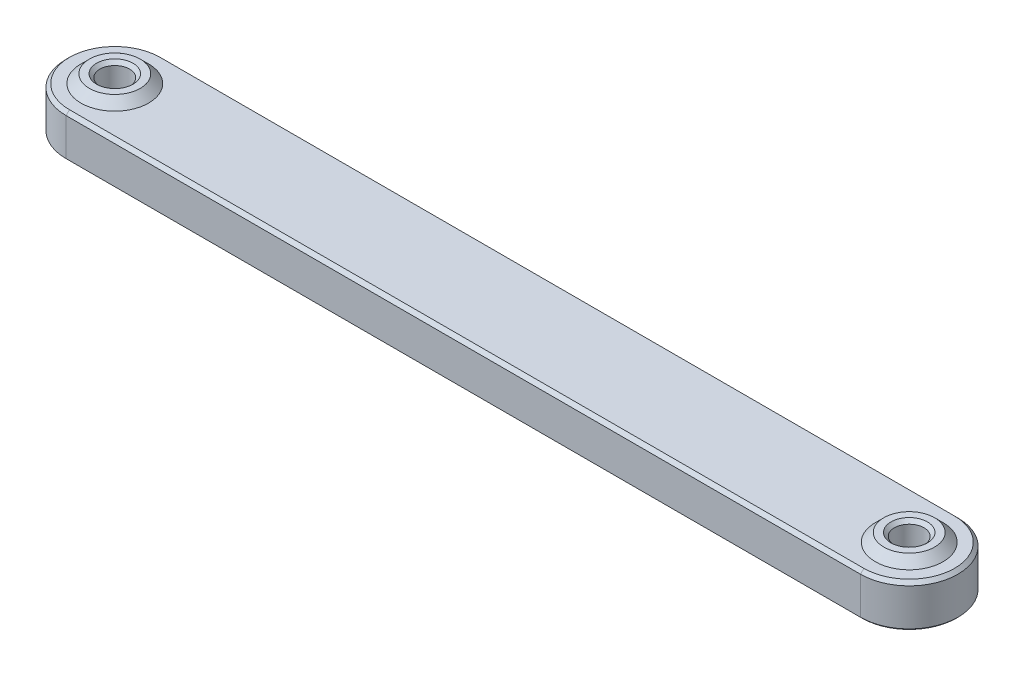
SolidWorks part; units mm, degrees
ref_plane "Alzado" through (0, 0, 0) normal (0, 0, 1) x (1, 0, 0)
ref_plane "Planta" through (0, 0, 0) normal (0, 1, 0) x (1, 0, 0)
ref_plane "Vista lateral" through (0, 0, 0) normal (1, 0, 0) x (0, 0, -1)
sketch "Croquis2" plane through (0, 0, 0) normal (0, 1, 0) x (1, 0, 0)
  line L0 (0, 0) -> (93.75, 0) construction
  line L1 (0, 5.75) -> (93.75, 5.75)
  line L2 (0, -5.75) -> (93.75, -5.75)
  arc A0 (0, 5.75) -> (0, -5.75) centre (0, 0) ccw
  arc A1 (93.75, -5.75) -> (93.75, 5.75) centre (93.75, 0) ccw
  circle A2 centre (93.75, 0) radius 1.75
  circle A3 centre (0, 0) radius 1.75
  point P3 (46.875, 0)
  dimension "D2" = 3.5
  dimension "D3" = 5.75
  dimension "D1" = 93.75
extrude "Saliente-Extruir1" add sketch "Croquis2" along normal blind 5 contours L2 A1 L1 A0 A3 A2 region at (46.875, 0, 0)
sketch "Croquis3" plane through (0, 5, 0) normal (0, 1, 0) x (1, 0, 0)
  circle A0 centre (93.75, 0) radius 3
  circle A1 centre (93.75, 0) radius 1.75 construction
  circle A2 centre (93.75, 0) radius 1.75
  circle A3 centre (0, 0) radius 3
  circle A4 centre (0, 0) radius 1.75 construction
  circle A5 centre (0, 0) radius 1.75
  dimension "D1" = 6
extrude "Saliente-Extruir2" add sketch "Croquis3" along normal blind 1
chamfer "Chaflán1" distance 1 angle 45 2 edges at (93.75, 5, 3) (0, 5, 3)
chamfer "Chaflán2" distance 0.4 angle 45 6 edges at (46.875, 5, -5.75) (-5.75, 5, 0) (99.5, 5, 0) (46.875, 5, 5.75) (93.75, 6, 1.75) (0, 6, 1.75)
sketch "Croquis4" plane through (0, 0, 0) normal (0, -1, 0) x (1, 0, 0)
  line L1 (93.75, 3.2043) -> (90.975, 1.6021)
  line L2 (90.975, 1.6021) -> (90.975, -1.6021)
  line L3 (90.975, -1.6021) -> (93.75, -3.2043)
  line L4 (93.75, -3.2043) -> (96.525, -1.6021)
  line L5 (96.525, -1.6021) -> (96.525, 1.6021)
  line L6 (96.525, 1.6021) -> (93.75, 3.2043)
  circle A0 centre (93.75, 0) radius 2.775 construction
  circle A1 centre (93.75, 3.2043) radius 0.4
  circle A2 centre (96.525, 1.6021) radius 0.4
  circle A3 centre (96.525, -1.6021) radius 0.4
  circle A4 centre (93.75, -3.2043) radius 0.4
  circle A5 centre (90.975, -1.6021) radius 0.4
  circle A6 centre (90.975, 1.6021) radius 0.4
  point P22 (93.75, 0)
  circle M9 centre (93.75, 0) radius 1.75
  dimension "D1" = 5.55
  dimension "D2" = 0.8
  dimension "D3" = 6
extrude "Cortar-Extruir1" cut sketch "Croquis4" against normal blind 2.3 contours A6 L2 A5 L3 A4 L4 A3 L5 A2 L6 A1 L1 M9 | L6 A1 L1 | L1 A1 L6 | L5 A2 L6 | L6 A2 L5 | L4 A3 L5 | L5 A3 L4 | L3 A4 L4 | L4 A4 L3 | L2 A5 L3 | L3 A5 L2 | L1 A6 L2 | L2 A6 L1 region at (93.75, 0, 2.9838) region at (93.75, 0, 3.3146) region at (93.75, 0, 2.7225) region at (91.166, 0, 1.4919) region at (90.8795, 0, 1.6573) region at (96.6205, 0, 1.6573) region at (96.334, 0, 1.4919) region at (91.166, 0, -1.4919) region at (90.8795, 0, -1.6573) region at (96.6205, 0, -1.6573) region at (96.334, 0, -1.4919) region at (93.75, 0, -2.9838) region at (93.75, 0, -3.3146)
chamfer "Chaflán3" distance 0.2 angle 45 17 edges at (99.5, 0, 0) (46.875, 0, -5.75) (-5.75, 0, 0) (46.875, 0, 5.75) (0, 0, 1.75) (90.6286, 0, -1.8021) (92.3625, 0, -2.4032) (93.75, 0, -3.6043) (95.1375, 0, -2.4032) (96.8714, 0, -1.8021) (96.525, 0, 0) (96.8714, 0, 1.8021) (95.1375, 0, 2.4032) (93.75, 0, 3.6043) (92.3625, 0, 2.4032) (90.6286, 0, 1.8021) (90.975, 0, 0)
sketch "Croquis5" plane through (0, 2.3, 0) normal (0, -1, 0) x (1, 0, 0)
  line L0 (92, 2.1939) -> (92, -2.1939)
  line L1 (93.4036, 3.0043) -> (91.3214, 1.8021) construction
  line L2 (91.3214, -1.8021) -> (93.4036, -3.0043) construction
  line L3 (93.75, 1.75) -> (93.75, -1.75) construction
  line L4 (95.5, 2.1939) -> (95.5, -2.1939)
  line L11 (90.975, 1.2021) -> (90.975, -1.2021)
  line L12 (91.3214, -1.8021) -> (93.4036, -3.0043)
  line L13 (94.0964, -3.0043) -> (96.1786, -1.8021)
  line L14 (96.525, -1.2021) -> (96.525, 1.2021)
  line L15 (96.1786, 1.8021) -> (94.0964, 3.0043)
  line L16 (93.4036, 3.0043) -> (91.3214, 1.8021)
  line L17 (90.975, 1.2021) -> (90.975, -1.2021)
  line L18 (91.3214, -1.8021) -> (93.4036, -3.0043)
  line L19 (94.0964, -3.0043) -> (96.1786, -1.8021)
  line L20 (96.525, -1.2021) -> (96.525, 1.2021)
  line L21 (96.1786, 1.8021) -> (94.0964, 3.0043)
  line L22 (93.4036, 3.0043) -> (91.3214, 1.8021)
  circle A0 centre (93.75, 0) radius 1.75 construction
  arc A7 (91.3214, 1.8021) -> (90.975, 1.2021) centre (90.975, 1.6021) ccw
  arc A8 (90.975, -1.2021) -> (91.3214, -1.8021) centre (90.975, -1.6021) ccw
  arc A9 (93.4036, -3.0043) -> (94.0964, -3.0043) centre (93.75, -3.2043) ccw
  arc A10 (96.1786, -1.8021) -> (96.525, -1.2021) centre (96.525, -1.6021) ccw
  arc A11 (96.525, 1.2021) -> (96.1786, 1.8021) centre (96.525, 1.6021) ccw
  arc A12 (94.0964, 3.0043) -> (93.4036, 3.0043) centre (93.75, 3.2043) ccw
  arc A13 (91.3214, 1.8021) -> (90.975, 1.2021) centre (90.975, 1.6021) ccw
  arc A14 (90.975, -1.2021) -> (91.3214, -1.8021) centre (90.975, -1.6021) ccw
  arc A15 (93.4036, -3.0043) -> (94.0964, -3.0043) centre (93.75, -3.2043) ccw
  arc A16 (96.1786, -1.8021) -> (96.525, -1.2021) centre (96.525, -1.6021) ccw
  arc A17 (96.525, 1.2021) -> (96.1786, 1.8021) centre (96.525, 1.6021) ccw
  arc A18 (94.0964, 3.0043) -> (93.4036, 3.0043) centre (93.75, 3.2043) ccw
  line M17 (91.3214, -1.8021) -> (93.4036, -3.0043)
  arc M18 (93.4036, -3.0043) -> (94.0964, -3.0043) centre (93.75, -3.2043) ccw
  line M19 (94.0964, -3.0043) -> (96.1786, -1.8021)
  line M23 (96.1786, 1.8021) -> (94.0964, 3.0043)
  arc M24 (94.0964, 3.0043) -> (93.4036, 3.0043) centre (93.75, 3.2043) ccw
  line M25 (93.4036, 3.0043) -> (91.3214, 1.8021)
  circle M26 centre (93.75, 0) radius 1.75
  dimension "D1" = 0
extrude "Cortar-Extruir2" cut sketch "Croquis5" against normal blind 0.2 contours L4 L0 M23 M24 M25 M26 | L4 L0 M26 M17 M18 M19 region at (93.75, 2.3, 2.0992) region at (93.75, 2.3, -2.0992)
sketch "Croquis6" plane through (0, 2.5, 0) normal (0, -1, 0) x (1, 0, 0)
  line L0 (92, 1.75) -> (95.5, 1.75)
  line L1 (92, 2.1939) -> (92, -2.1939) construction
  line L2 (95.5, 2.1939) -> (95.5, 0) construction
  line L3 (92, 0) -> (95.5, 0) construction
  line L4 (92, -1.75) -> (95.5, -1.75)
  line L5 (95.5, 0) -> (95.5, 2.1939) construction
  line L6 (95.5, 2.1939) -> (94.0964, 3.0043) construction
  line L7 (93.4036, 3.0043) -> (92, 2.1939) construction
  line L8 (92, 2.1939) -> (92, 0) construction
  line L9 (95.5, -2.1939) -> (95.5, 0) construction
  line L10 (92, 0) -> (92, -2.1939) construction
  line L11 (92, -2.1939) -> (93.4036, -3.0043) construction
  line L12 (94.0964, -3.0043) -> (95.5, -2.1939) construction
  line L13 (95.5, 0) -> (95.5, 2.1939)
  line L14 (95.5, 2.1939) -> (94.0964, 3.0043)
  line L15 (93.4036, 3.0043) -> (92, 2.1939)
  line L16 (92, 2.1939) -> (92, 0)
  line L17 (95.5, -2.1939) -> (95.5, 0)
  line L18 (92, 0) -> (92, -2.1939)
  line L19 (92, -2.1939) -> (93.4036, -3.0043)
  line L20 (94.0964, -3.0043) -> (95.5, -2.1939)
  arc A0 (95.5, 0) -> (92, 0) centre (93.75, 0) ccw construction
  arc A1 (94.0964, 3.0043) -> (93.4036, 3.0043) centre (93.75, 3.2043) ccw construction
  arc A2 (92, 0) -> (95.5, 0) centre (93.75, 0) ccw construction
  arc A3 (93.4036, -3.0043) -> (94.0964, -3.0043) centre (93.75, -3.2043) ccw construction
  arc A4 (94.0964, 3.0043) -> (93.4036, 3.0043) centre (93.75, 3.2043) ccw
  arc A5 (95.5, 0) -> (92, 0) centre (93.75, 0) ccw
  arc A6 (92, 0) -> (95.5, 0) centre (93.75, 0) ccw
  arc A7 (93.4036, -3.0043) -> (94.0964, -3.0043) centre (93.75, -3.2043) ccw
  line M3 (95.5, 0) -> (95.5, 2.1939)
  line M7 (92, 2.1939) -> (92, 0)
  arc M8 (92, 0) -> (95.5, 0) centre (93.75, 0) cw
extrude "Cortar-Extruir3" cut sketch "Croquis6" against normal blind 0.2 contours L0 M7 M8 | L0 M8 M3 | A6 L4 L17 | A6 L18 L4 region at (92.3909, 2.5, 1.3591) region at (95.1091, 2.5, 1.3591) region at (92.3909, 2.5, -1.3591) region at (95.1091, 2.5, -1.3591)
chamfer "Chaflán4" distance 0.4 angle 45 4 edges at (94.9874, 2.7, -1.2374) (92.5126, 2.7, -1.2374) (94.9874, 2.7, 1.2374) (92.5126, 2.7, 1.2374)
